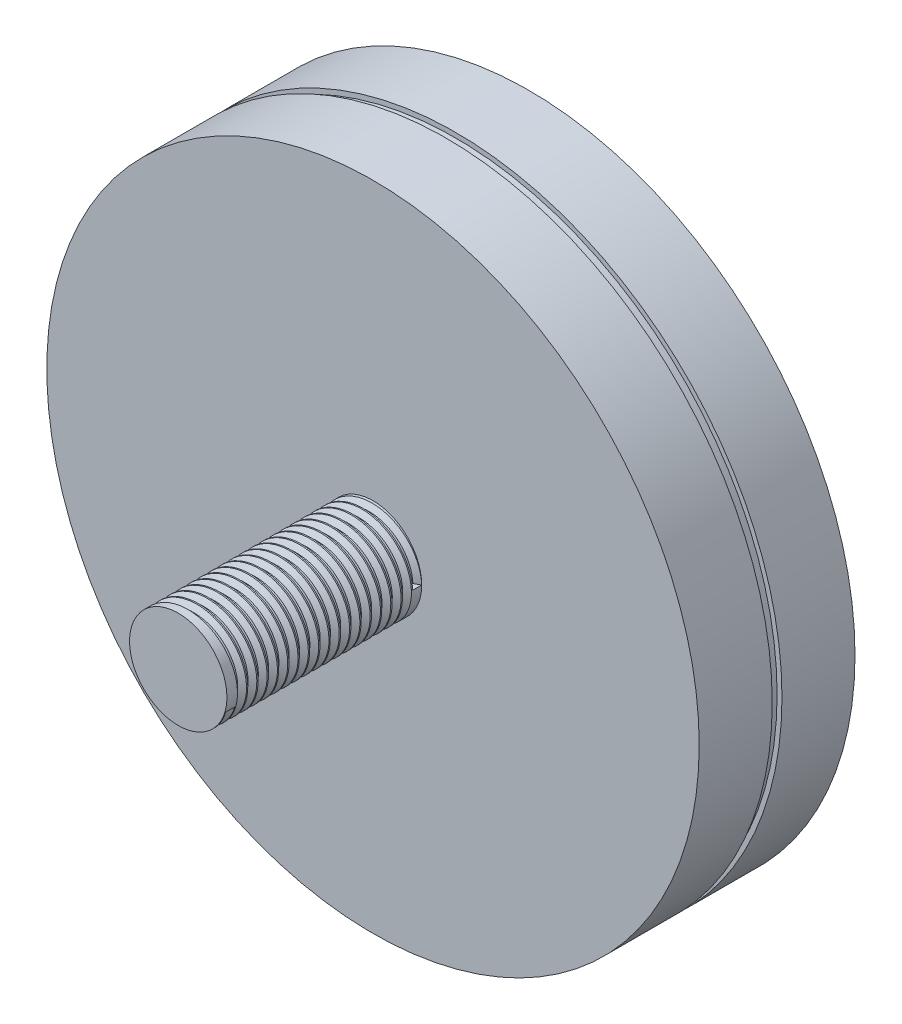
SolidWorks part; units mm, degrees
ref_plane "Front Plane" through (0, 0, 0) normal (0, 0, 1) x (1, 0, 0)
ref_plane "Top Plane" through (0, 0, 0) normal (0, 1, 0) x (1, 0, 0)
ref_plane "Right Plane" through (0, 0, 0) normal (1, 0, 0) x (0, 0, -1)
sketch "Sketch1" plane through (0, 0, 0) normal (0, 0, 1) x (1, 0, 0)
  circle A0 centre (0, 0) radius 33.5
  dimension "D1" = 67
extrude "Boss-Extrude1" add sketch "Sketch1" along normal blind 7.5
sketch "Sketch2" plane through (0, 0, 7.5) normal (0, 0, 1) x (1, 0, 0)
  circle A0 centre (0, 0) radius 33
  dimension "D1" = 66
extrude "Boss-Extrude2" add sketch "Sketch2" along normal blind 1 contours A0
sketch "Sketch3" plane through (0, 0, 8.5) normal (0, 0, 1) x (1, 0, 0)
  circle A0 centre (0, 0) radius 33.5
extrude "Boss-Extrude3" add sketch "Sketch3" along normal blind 7.5
sketch "Sketch4" plane through (0, 0, 16) normal (0, 0, 1) x (1, 0, 0)
  circle A0 centre (0, 0) radius 5
  dimension "D1" = 10
extrude "Boss-Extrude4" add sketch "Sketch4" along normal blind 20
thread "螺纹线1" pitch 1.0583 method cut profile "螺纹线轮廓1" start angle 0, offset 0, length 19, pitch 1.0583, diameter 10
ref_plane "基准面1" through (5, 0, 16) normal (0, -1, 0) x (1, 0, 0)
sketch "螺纹线轮廓1" plane through (5, 0, 16) normal (0, -1, 0) x (1, 0, 0)
  line L0 (0, 0) -> (0, 1.0583) construction
  line L11 (0, 0) -> (0, 0.926)
  line L12 (0, 0.926) -> (-0.5728, 0.5953)
  line L13 (-0.5728, 0.5953) -> (-0.5728, 0.3307)
  line L15 (-0.5728, 0.3307) -> (0, 0)
  line L17 (-0.5728, 0.463) -> (0, 0.463) construction
  point P2 (0, 0)
  dimension "Pitch" = 1.0583
  dimension "Profile_Angle" = 60
  dimension "Profile_Land" = 0.2646
  dimension "Profile_Height" = 0.5728
